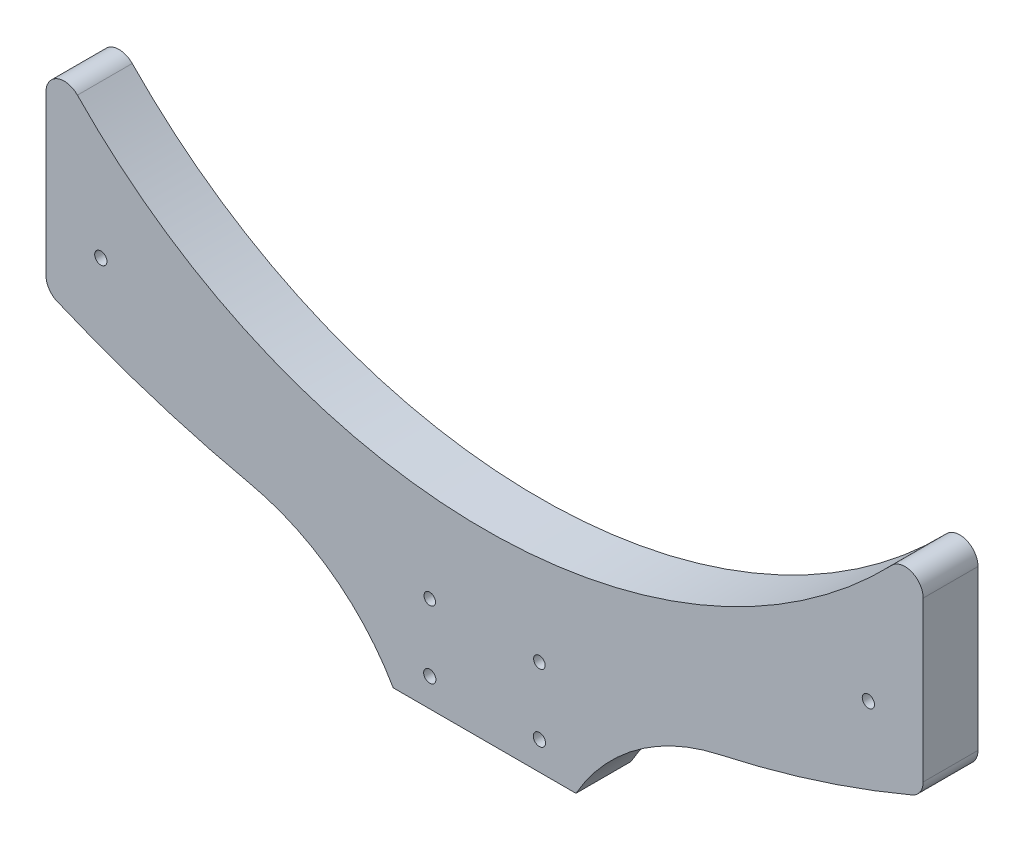
SolidWorks part; units mm, degrees
ref_plane "Front Plane" through (0, 0, 0) normal (0, 0, 1) x (1, 0, 0)
ref_plane "Top Plane" through (0, 0, 0) normal (0, 1, 0) x (1, 0, 0)
ref_plane "Right Plane" through (0, 0, 0) normal (1, 0, 0) x (0, 0, -1)
sketch "Sketch1" plane through (0, 0, 0) normal (0, 0, 1) x (1, 0, 0)
  line L0 (0, 0) -> (0, -76.2)
  line L1 (304.8, 0) -> (304.8, -76.2)
  line L2 (152.4, -1108.0077) -> (152.4, 48891.9923) construction
  line L3 (-847.6, -108.0077) -> (49152.4, -108.0077) construction
  arc A0 (0, 0) -> (304.8, 0) centre (152.4, 124.596) ccw
  arc A2 (0, -76.2) -> (304.8, -76.2) centre (152.4, 272.9923) ccw
  circle A3 centre (19.05, -57.2077) radius 2.125
  circle A4 centre (285.75, -57.2077) radius 2.125
  point P10 (152.4, -108.0077)
  dimension "D2" = 196.85
  dimension "D3" = 381
  dimension "D4" = 304.8
  dimension "D6" = 4.25
  dimension "D1" = 304.8
  dimension "D5" = 76.2
  dimension "D7" = 133.35
  dimension "D8" = 50.8
extrude "Boss-Extrude1" add sketch "Sketch1" along normal blind 19.05
fillet "Fillet1" radius 6.35 2 edges at (304.8, 0, 9.525) (0, 0, 9.525)
fillet "Fillet2" radius 6.35 2 edges at (0, -76.2, 9.525) (304.8, -76.2, 9.525)
sketch "Sketch3" plane through (0, 0, 19.05) normal (0, 0, 1) x (1, 0, 0)
  line L0 (0, -64.478) -> (304.8, -64.478) construction
  line L1 (0, -16.6826) -> (0, -72.0179) construction
  line L2 (304.8, -72.0179) -> (304.8, -16.6826) construction
  line L3 (152.4, -1064.478) -> (152.4, 48935.522) construction
  line L5 (120.65, -72.254) -> (184.15, -72.254)
  line L6 (120.65, -72.254) -> (120.65, -135.754)
  line L7 (120.65, -135.754) -> (184.15, -135.754)
  line L8 (184.15, -72.254) -> (184.15, -135.754)
  arc A0 (10.9141, -12.2676) -> (293.8859, -12.2676) centre (152.4, 124.596) ccw construction
  point P9 (152.4, -64.478)
  point P13 (152.4, -72.254)
  dimension "D1" = 63.5
  dimension "D2" = 63.5
extrude "Boss-Extrude2" add sketch "Sketch3" against normal up to surface (19.05 mm away) up to face at (152.4, -55.2006, 0)
fillet "Fillet3" radius 76.2 2 edges at (184.15, -106.6825, 9.525) (120.65, -106.6825, 9.525)
sketch "Sketch8" plane through (0, 0, 0) normal (0, 0, -1) x (-1, 0, 0)
  line L0 (-152.4, -1162.419) -> (-152.4, 48837.581) construction
  line L1 (-184.15, -135.754) -> (-120.65, -135.754) construction
  circle A0 centre (-171.45, -125.9023) radius 2.125
  circle A1 centre (-133.35, -125.9023) radius 2.125
  circle A2 centre (-171.45, -125.9023) radius 2.85 construction
  point P7 (-152.4, -135.754)
  dimension "D1" = 4.25
extrude "Cut-Extrude3" cut sketch "Sketch8" against normal blind 19.05
sketch "Sketch10" plane through (0, 0, 19.05) normal (0, 0, 1) x (1, 0, 0)
  circle A0 centre (133.35, -102.619) radius 2
  circle A1 centre (171.45, -102.619) radius 2
  dimension "D1" = 4
extrude "Cut-Extrude7" cut sketch "Sketch10" against normal through all
